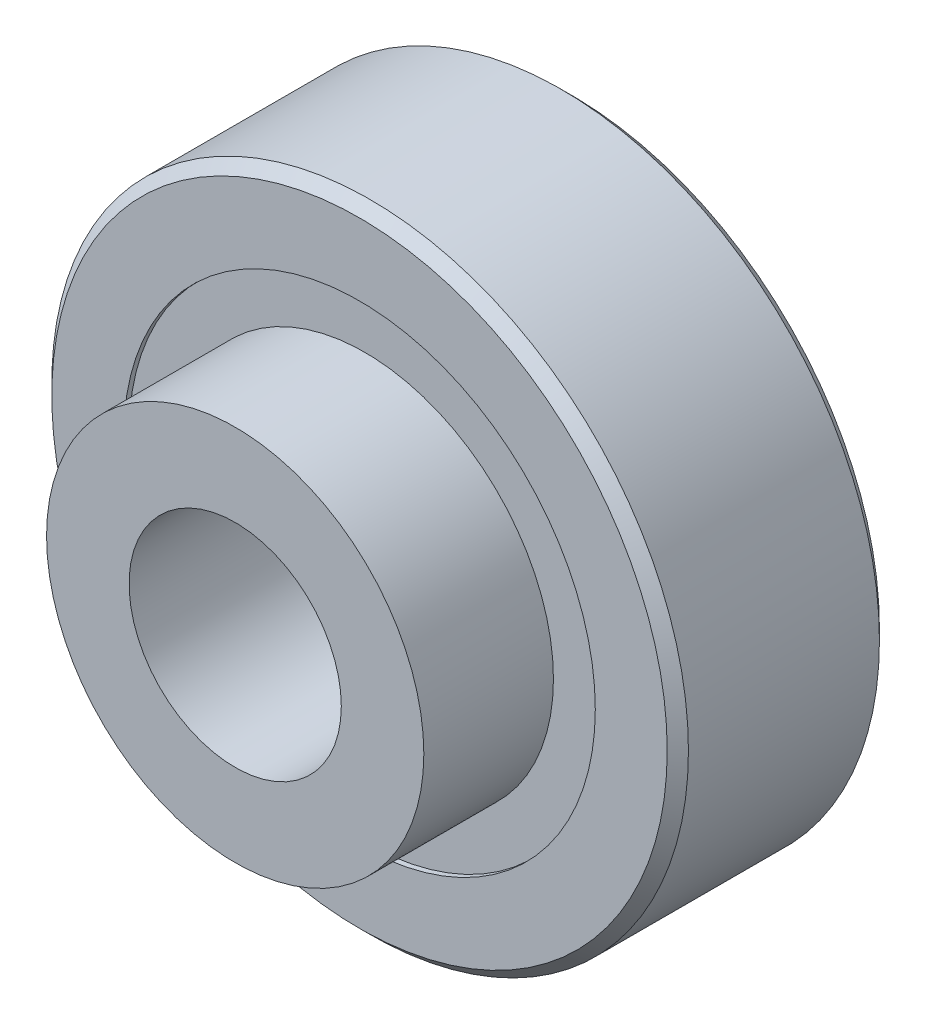
SolidWorks part; units mm, degrees
ref_plane "Front Plane" through (0, 0, 0) normal (0, 0, 1) x (1, 0, 0)
ref_plane "Top Plane" through (0, 0, 0) normal (0, 1, 0) x (1, 0, 0)
ref_plane "Right Plane" through (0, 0, 0) normal (1, 0, 0) x (0, 0, -1)
sketch "Outter Chase Sketch" plane through (0, 0, 0) normal (1, 0, 0) x (0, 0, -1)
  line L0 (-3.5, 0) -> (3.5, 0) construction
  line L1 (0, 10.5) -> (0, -10.5) construction
  line L2 (3.15, 10.5) -> (-3.15, 10.5)
  line L3 (-3.15, 10.5) -> (-3.5, 10.15)
  line L4 (-3.5, 10.15) -> (-3.5, 7.7778)
  line L5 (-3.5, 7.7778) -> (-1.5556, 7.7778)
  line L6 (3.5, 7.7778) -> (1.5556, 7.7778)
  line L7 (3.5, 10.15) -> (3.5, 7.7778)
  line L8 (3.15, 10.5) -> (3.5, 10.15)
  line L9 (0, 10.5) -> (0, 7) construction
  line L10 (0, 7) -> (0, 3.5) construction
  arc A0 (-1.5556, 7.7778) -> (1.5556, 7.7778) centre (0, 7) cw
  point P14 (0, 3.5)
  dimension "Width" = 7
  dimension "OD" = 21
  dimension "D1" = 45
  dimension "D2" = 0.35
  dimension "ID" = 7
  dimension "D3" = 3.1111
  dimension "D4" = 0.7778
revolve "Outter Chase Revolve" add sketch "Outter Chase Sketch" angle 360 about L0
sketch "Inner Chase Sketch" plane through (0, 0, 0) normal (1, 0, 0) x (0, 0, -1)
  line L0 (-3.5, 6.2222) -> (-1.5556, 6.2222)
  line L1 (0, 10.5) -> (0, -10.5) construction
  line L2 (-3.5, 10.15) -> (-3.5, 7.7778) construction
  line L3 (-3.5, 6.2222) -> (-3.5, 3.85)
  line L4 (-3.15, 10.5) -> (-3.5, 10.15) construction
  line L5 (-3.5, 3.85) -> (-3.15, 3.5)
  line L6 (-3.15, 3.5) -> (3.15, 3.5)
  line L7 (3.15, 10.5) -> (3.15, -10.5) construction
  line L8 (3.15, 3.5) -> (3.5, 3.85)
  line L9 (3.5, -10.15) -> (3.5, 10.15) construction
  line L10 (3.5, 3.85) -> (3.5, 6.2222)
  line L11 (3.5, 6.2222) -> (1.5556, 6.2222)
  line L13 (3.15, 10.5) -> (3.5, 10.15) construction
  arc A0 (1.5556, 7.7778) -> (-1.5556, 7.7778) centre (0, 7) ccw construction
  arc A1 (1.5556, 6.2222) -> (-1.5556, 6.2222) centre (0, 7) cw
revolve "Inner Chase Revolve" add sketch "Inner Chase Sketch" angle 360 about L0
sketch "Flange Sketch" plane through (0, 0, 0) normal (1, 0, 0) x (0, 0, -1)
  line L0 (-3.15, 3.5) -> (-3.5, 3.85)
  line L1 (-3.5, 3.85) -> (-3.5, 6.2222)
  line L2 (-3.5, 6.2222) -> (-7.6, 6.2222)
  line L3 (-7.6, 6.2222) -> (-7.6, 3.5)
  line L4 (-7.6, 3.5) -> (-3.15, 3.5)
  line L5 (3.5, 3.85) -> (3.5, 6.2222) construction
  dimension "Flange Height" = 11.1
revolve "Flange Revolve" add sketch "Flange Sketch" angle 360 about L0
sketch "Bearing Sketch" plane through (0, 0, 0) normal (1, 0, 0) x (0, 0, -1)
  line L0 (-1.7392, 7) -> (1.7392, 7)
  arc A2 (-1.7392, 7) -> (1.7392, 7) centre (0, 7) cw
  arc A3 (1.5556, 7.7778) -> (-1.5556, 7.7778) centre (0, 7) ccw construction
revolve "Bearing Revolve" [suppressed] add sketch "Bearing Sketch" angle 360 about L0
ref_axis "Axis1" through (0, 0, -3.5) along (0, 0, 1)
pattern_circular "Bearing Pattern" [suppressed] count 12 every 30 about axis through (0, 0, -3.5) along (0, 0, 1) of bodies 104
sketch "Cover 1 Sketch" plane through (0, 0, 0) normal (1, 0, 0) x (0, 0, -1)
  line L0 (-3.5, 7.7778) -> (-1.5556, 7.7778) construction
  line L1 (-3.325, 7.7778) -> (-1.7392, 7.7778)
  line L2 (-3.325, 7.7778) -> (-3.325, 6.2222)
  line L3 (-3.325, 6.2222) -> (-1.7392, 6.2222)
  line L4 (-1.7392, 7.7778) -> (-1.7392, 6.2222)
  line L5 (-3.5, 6.2222) -> (-1.5556, 6.2222) construction
  line L12 (-3.15, 10.5) -> (-3.5, 10.15) construction
  point P18 (-3.325, 10.325)
revolve "Cover 1 Revolve" add sketch "Cover 1 Sketch" angle 360 about L0
sketch "Cover 2 Sketch" plane through (0, 0, 0) normal (1, 0, 0) x (0, 0, -1)
  line L0 (1.7392, 6.2222) -> (3.325, 6.2222)
  line L1 (3.325, 6.2222) -> (3.325, 7.7778)
  line L2 (3.325, 7.7778) -> (1.7392, 7.7778)
  line L3 (1.7392, 7.7778) -> (1.7392, 6.2222)
  line L4 (3.5, 7.7778) -> (1.5556, 7.7778) construction
  line L5 (3.5, 6.2222) -> (1.5556, 6.2222) construction
  line L6 (3.15, 10.5) -> (3.5, 10.15) construction
  point P8 (3.325, 10.325)
revolve "Cover 2 Revolve" add sketch "Cover 2 Sketch" angle 360 about L0
equation "\"D2@Outter Chase Sketch\" = \"Width@Outter Chase Sketch\" * .05"
equation "\"D3@Outter Chase Sketch\" = \"Width@Outter Chase Sketch\" / 2.25"
equation "\"D4@Outter Chase Sketch\"=( \"OD@Outter Chase Sketch\" - \"Width@Outter Chase Sketch\" )  / 2 / 3/ 3"
equation "\"D2@Bearing Pattern\" = 360 / \"Balls@Bearing Pattern\""
